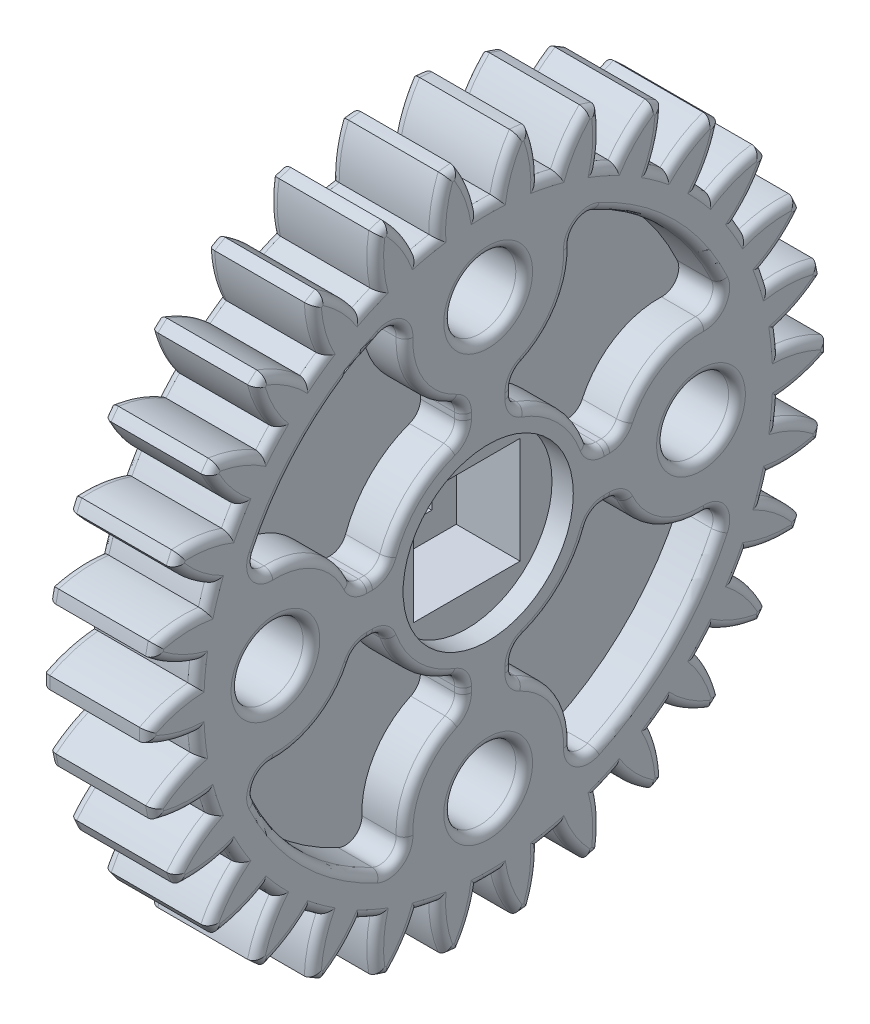
SolidWorks part; units mm, degrees
note: The reader was unsure of these and kept them because the rebuilt part matched: shared geometry of "Sketch2<4>", "Sketch3<3>".
ref_plane "Plane1" through (0, 0, 0) normal (0, 0, 1) x (1, 0, 0)
ref_plane "Plane2" through (0, 0, 0) normal (0, 1, 0) x (1, 0, 0)
ref_plane "Plane3" through (0, 0, 0) normal (1, 0, 0) x (0, 0, -1)
sketch "HoldingSke" plane through (0, 0, 0) normal (0, 1, 0) x (1, 0, 0)
  line L0 (0, 0) -> (439.9409, -254)
  line L1 (-15, 0) -> (100, 0) construction
  line L2 (0, 0) -> (-2.1039, 2.3779)
  line L3 (0, 0) -> (-11.863, 4.5341)
  line L4 (0, 0) -> (7.479, 4.318)
  line L5 (0, 0) -> (-47.5972, -17.7524)
  line L6 (0, 0) -> (-5.2639, -3.5516)
  line L7 (-2.1039, 2.3779) -> (8.8308, 51.9871)
  line L8 (-76.2, 54.61) -> (-74.422, 54.61)
  line L9 (-71.009, 38.7566) -> (-53.1078, 45.2721)
  line L10 (-76.2, 71.12) -> (104.1128, 71.12)
  line L11 (0, 0) -> (-6.35, 0)
  line L12 (-76.2, 101.6) -> (-76.1492, 101.6)
  line L13 (24.9733, 27.94) -> (52.9518, 28.4284)
  line L14 (24.9733, 27.94) -> (25.0241, 27.9398)
  line L15 (24.9733, 27.94) -> (100.4021, 29.52)
  circle A0 centre (0, 0) radius 0.7937
  circle A1 centre (0, 0) radius 17.4752
  circle A2 centre (0, 0) radius 38.1
  circle A3 centre (0, 0) radius 0.7937
  dimension "MHD" = 34.9504
  dimension "Hub_dia" = 76.2
  dimension "Bore" = 1.5875
  dimension "MBD" = 1.5875
  dimension "Num_teeth" = 30
  dimension "Pitch" = 508
  dimension "Overall_len" = 50.8
  dimension "Show_teeth" = 30
  dimension "Thickness" = 6.35
  dimension "OAL" = 50.8001
  dimension "T_dim" = 1.778
  dimension "Ap" = 20
  dimension "H" = 19.05
  dimension "Pitch_radius" = 180.3128
  dimension "Width" = 6.35
  dimension "Backlash" = 0.0508
  dimension "Addendum_fac" = 1
  dimension "Dedendum_fac" = 1.2
  dimension "Clearance_fac" = 0.2
  dimension "Dedendum_add" = 0.0508
sketch "BasProSke" plane through (0, 0, 0) normal (0, 1, 0) x (1, 0, 0)
  line L0 (-10, 0) -> (60, 0) construction
  line L1 (0, 0) -> (0, 20.32)
  line L2 (0, 0) -> (6.35, 0)
  line L3 (6.35, 0) -> (6.35, 20.32)
  line L4 (6.35, 20.32) -> (0, 20.32)
  dimension "Thickness" = 6.35
  dimension "Diameter" = 40.64
revolve "Base-Revolve" add sketch "BasProSke" angle 360 about L0
sketch "TooCutSke" plane through (0, 0, 0) normal (1, 0, 0) x (0, 0, -1)
  line L1 (0, 0) -> (0, 107) construction
  line L2 (0, 0) -> (-1.0859, 19.019) construction
  line L3 (0, 0) -> (-3.978, 37.8482) construction
  line L4 (-1.0859, 19.019) -> (-1.989, 18.9241) construction
  arc A0 (0.5992, 17.4649) -> (-0.5992, 17.4649) centre (0, 0) ccw
  arc A1 (1.7751, 20.2678) -> (-1.7751, 20.2678) centre (0, 0) ccw
  circle A2 centre (0, 0) radius 19.05 construction
  circle A3 centre (0, 0) radius 17.9011 construction
  arc A4 (-0.5992, 17.4649) -> (-1.7751, 20.2678) centre (-8.0726, 15.9776) ccw
  arc A5 (1.7751, 20.2678) -> (0.5992, 17.4649) centre (8.0726, 15.9776) ccw
  dimension "Root_dia" = 34.9504
  dimension "Overcut_dia" = 40.6908
  dimension "Pitch_dia" = 38.1
  dimension "Base_dia" = 35.8023
  dimension "Flank_rad" = 7.62
  dimension "Half_ang" = 6
  dimension "Half_CT" = 0.9081
extrude "ToothCut" cut sketch "TooCutSke" along normal through all
fillet "Breaks" [suppressed] radius 0.0254
fillet "RootFillets" [suppressed] radius 0.3048
pattern_circular "TeethCuts" count 30 every 12 about axis through (-10, 0, 0) along (1, 0, 0) of "ToothCut", "RootFillets", "Breaks"
sketch "HubNeaOneSke" plane through (0, 0, 0) normal (-1, 0, 0) x (0, 0, 1)
  circle A0 centre (0, 0) radius 17.4752
  dimension "Diameter" = 34.9504
extrude "HubNearOne" [suppressed] add sketch "HubNeaOneSke" along normal blind 44.4501
sketch "HubNeaBotSke" plane through (0, 0, 0) normal (-1, 0, 0) x (0, 0, 1)
  circle A0 centre (0, 0) radius 17.4752
  dimension "Diameter" = 34.9504
extrude "HubNearBoth" [suppressed] add sketch "HubNeaBotSke" along normal blind 22.225
ref_plane "FarPln" through (6.35, 0, 0) normal (1, 0, 0) x (0, 0, -1)
sketch "HubFarSke" plane through (6.35, 0, 0) normal (1, 0, 0) x (0, 0, -1)
  circle A0 centre (0, 0) radius 17.4752
  dimension "Diameter" = 34.9504
extrude "HubFar" [suppressed] add sketch "HubFarSke" along normal blind 22.225
sketch "BorSke" plane through (0, 0, 0) normal (1, 0, 0) x (0, 0, -1)
  circle A0 centre (0, 0) radius 0.7937
  dimension "Diameter" = 1.5875
extrude "Bore" cut sketch "BorSke" along normal mid plane 101.6001
sketch "KeySke" plane through (0, 0, 0) normal (1, 0, 0) x (0, 0, -1)
  line L0 (-0.127, 0) -> (-0.127, 0.9843)
  line L1 (-0.127, 0.9843) -> (0.127, 0.9843)
  line L2 (0.127, 0.9843) -> (0.127, 0)
  line L3 (0, 0) -> (0, 34) construction
  line L4 (-0.127, 0) -> (0.127, 0)
  dimension "Offset" = 0.9843
  dimension "Width" = 0.254
extrude "Keyway" [suppressed] cut sketch "KeySke" along normal mid plane 101.6001
pattern_circular "Keyway2" [suppressed] count 2 every 90 about axis through (-10, 0, 0) along (1, 0, 0)
sketch "Sketch1" plane through (6.35, 0, 0) normal (1, 0, 0) x (0, 0, -1)
  line L1 (1.7145, 1.7145) -> (-1.7145, 1.7145)
  line L2 (1.7145, 1.7145) -> (1.7145, -1.7145)
  line L3 (1.7145, -1.7145) -> (-1.7145, -1.7145)
  line L4 (-1.7145, 1.7145) -> (-1.7145, -1.7145)
  line L5 (1.7145, 1.7145) -> (-1.7145, -1.7145) construction
  line L6 (1.7145, -1.7145) -> (-1.7145, 1.7145) construction
  point P0 (0, 0)
  dimension "D1" = 3.429
extrude "Cut-Extrude1" cut sketch "Sketch1" against normal up to next
sketch "Sketch2" plane through (6.35, 0, 0) normal (1, 0, 0) x (0, 0, -1)
  line L0 (0, 0) -> (0, 10.2796) construction
  line L1 (-7.9303, -1.5) -> (-6.1703, -1.5)
  line L2 (-7.9303, 1.5) -> (-6.1703, 1.5)
  line L3 (1.5, -7.9303) -> (1.5, -6.1703)
  line L4 (-1.5, 7.9303) -> (-1.5, 6.1703)
  line L5 (1.5, 7.9303) -> (1.5, 6.1703)
  line L6 (7.9303, 1.5) -> (6.1703, 1.5)
  line L7 (7.9303, -1.5) -> (6.1703, -1.5)
  line L17 (-1.5, -7.9303) -> (-1.5, -6.1703)
  circle A0 centre (0, 0) radius 6.35
  circle A1 centre (0, 0) radius 15.24
  arc A2 (4.661, -14.5097) -> (1.5, -7.9303) centre (0, -12.7) ccw
  circle A3 centre (0, -12.7) radius 2.15
  arc A4 (-1.5, -7.9303) -> (-4.661, -14.5097) centre (0, -12.7) ccw
  arc A5 (-14.5097, -4.661) -> (-7.9303, -1.5) centre (-12.7, 0) ccw
  circle A6 centre (-12.7, 0) radius 2.15
  arc A7 (-7.9303, 1.5) -> (-14.5097, 4.661) centre (-12.7, 0) ccw
  arc A8 (-4.661, 14.5097) -> (-1.5, 7.9303) centre (0, 12.7) ccw
  circle A9 centre (0, 12.7) radius 2.15
  arc A10 (1.5, 7.9303) -> (4.661, 14.5097) centre (0, 12.7) ccw
  arc A11 (14.5097, 4.661) -> (7.9303, 1.5) centre (12.7, 0) ccw
  circle A12 centre (12.7, 0) radius 2.15
  arc A13 (7.9303, -1.5) -> (14.5097, -4.661) centre (12.7, 0) ccw
  dimension "D2" = 12.7
  dimension "D3" = 30.48
  dimension "D1" = 4.3
  dimension "D6" = 5
  dimension "D5" = 12.7
  dimension "D4" = 3
  dimension "D7" = 4
extrude "Cut-Extrude2" cut sketch "Sketch2" against normal through all contours A5 A1 A4 L17 A0 L1 | A13 L7 A0 L3 A2 A1 | A11 A1 A10 L5 A0 L6 | A8 A1 A7 L2 A0 L4 | A6 | L0 A3 | A3 L0 | A12 | L0 A9 | A9 L0
fillet "Fillet2" radius 1 24 edges at (3.175, -6.1703, -1.5) (3.175, -4.661, -14.5097) (3.175, -14.5097, -4.661) (3.175, -7.9303, -1.5) (3.175, -1.5, -6.1703) (3.175, -1.5, -7.9303) (3.175, 4.661, -14.5097) (3.175, 1.5, -7.9303) (3.175, 1.5, -6.1703) (3.175, 6.1703, -1.5) (3.175, 7.9303, -1.5) (3.175, 14.5097, -4.661) (3.175, 14.5097, 4.661) (3.175, 7.9303, 1.5) (3.175, 6.1703, 1.5) (3.175, 4.661, 14.5097) (3.175, 1.5, 7.9303) (3.175, 1.5, 6.1703) (3.175, -14.5097, 4.661) (3.175, -7.9303, 1.5) (3.175, -4.661, 14.5097) (3.175, -1.5, 7.9303) (3.175, -6.1703, 1.5) (3.175, -1.5, 6.1703)
extrude "Boss-Extrude1" add sketch "Sketch2<4>" along normal mid plane 1.27 from offset 3.175 offset against normal yes
sketch "Sketch2<4>" plane through (6.35, 0, 0) normal (1, 0, 0) x (0, 0, -1) same geometry as "Sketch2"
fillet "Fillet3" radius 0.5 352 edges at (0, -3.0115, 18.6998) (6.35, 19.3255, -6.2792) (6.35, 17.5976, -10.16) (6.35, 15.1007, -13.5967) (6.35, 11.9438, -16.4392) (6.35, 8.2649, -18.5632) (6.35, 4.2248, -19.876) (6.35, 0, -20.32) (6.35, -4.2248, -19.876) (6.35, -8.2649, -18.5632) (6.35, -11.9438, -16.4392) (6.35, -15.1007, -13.5967) (6.35, -17.5976, -10.16) (6.35, 20.2087, -2.124) (6.35, -19.3255, -6.2792) (6.35, -20.2087, -2.124) (6.35, -20.2087, 2.124) (6.35, -19.3255, 6.2792) (6.35, -17.5976, 10.16) (6.35, -15.1007, 13.5967) (6.35, -11.9438, 16.4392) (6.35, -8.2649, 18.5632) (6.35, -4.2248, 19.876) (6.35, 0, 20.32) (6.35, 4.2248, 19.876) (6.35, 8.2649, 18.5632) (6.35, 11.9438, 16.4392) (6.35, 15.1007, 13.5967) (6.35, 17.5976, 10.16) (6.35, 19.3255, 6.2792) (6.35, 18.9122, -1.0403) (6.35, 18.9122, 1.0403) (6.35, 17.4752, 0) (0, 18.9122, -1.0403) (0, 17.4752, 0) (6.35, -0.9422, 18.9173) (6.35, -3.0115, 18.6998) (6.35, -1.8267, 17.3795) (0, -0.9422, 18.9173) (0, -1.8267, 17.3795) (6.35, 3.0115, 18.6998) (6.35, 0.9422, 18.9173) (6.35, 1.8267, 17.3795) (0, 3.0115, 18.6998) (0, 1.8267, 17.3795) (6.35, 6.8336, 17.6651) (6.35, 4.8548, 18.308) (6.35, 5.4001, 16.6199) (0, 6.8336, 17.6651) (0, 5.4001, 16.6199) (6.35, 10.357, 15.8583) (6.35, 8.5551, 16.8986) (6.35, 8.7376, 15.134) (0, 10.357, 15.8583) (0, 8.7376, 15.134) (6.35, 17.7003, 6.7419) (6.35, 16.854, 8.6427) (6.35, 15.9644, 7.1078) (0, 17.7003, 6.7419) (0, 15.9644, 7.1078) (6.35, 13.4278, 13.3584) (6.35, 11.8816, 14.7506) (6.35, 11.6932, 12.9866) (0, 13.4278, 13.3584) (0, 11.6932, 12.9866) (6.35, 15.9118, 10.2747) (6.35, 14.6888, 11.9579) (6.35, 14.1377, 10.2717) (0, 15.9118, 10.2747) (0, 14.1377, 10.2717) (6.35, -18.9122, 1.0403) (6.35, -18.9122, -1.0403) (6.35, -17.4752, 0) (0, -18.9122, 1.0403) (0, -17.4752, 0) (6.35, -18.2826, 4.9497) (6.35, -18.7152, 2.9145) (6.35, -17.0933, 3.6333) (0, -18.2826, 4.9497) (0, -17.0933, 3.6333) (6.35, -14.6888, 11.9579) (6.35, -15.9118, 10.2747) (6.35, -14.1377, 10.2717) (0, -14.6888, 11.9579) (0, -14.1377, 10.2717) (6.35, -16.854, 8.6427) (6.35, -17.7003, 6.7419) (6.35, -15.9644, 7.1078) (0, -16.854, 8.6427) (0, -15.9644, 7.1078) (0, 20.2087, 2.124) (6.35, -8.5551, 16.8986) (6.35, -10.357, 15.8583) (6.35, -8.7376, 15.134) (0, -8.5551, 16.8986) (0, -8.7376, 15.134) (0, 18.2826, 4.9497) (6.35, -11.8816, 14.7506) (6.35, -13.4278, 13.3584) (6.35, -11.6932, 12.9866) (0, -11.8816, 14.7506) (0, -11.6932, 12.9866) (6.35, 20.2087, 2.124) (6.35, -4.8548, 18.308) (6.35, -6.8336, 17.6651) (6.35, -5.4001, 16.6199) (0, -4.8548, 18.308) (0, -5.4001, 16.6199) (6.35, -3.0115, -18.6998) (6.35, -0.9422, -18.9173) (6.35, -1.8267, -17.3795) (0, -3.0115, -18.6998) (0, -1.8267, -17.3795) (6.35, -6.8336, -17.6651) (6.35, -4.8548, -18.308) (6.35, -5.4001, -16.6199) (0, -6.8336, -17.6651) (0, -5.4001, -16.6199) (6.35, 18.7152, 2.9145) (6.35, 18.2826, 4.9497) (6.35, -13.4278, -13.3584) (6.35, -11.8816, -14.7506) (6.35, -11.6932, -12.9866) (6.35, 17.0933, 3.6333) (0, -13.4278, -13.3584) (0, -11.6932, -12.9866) (0, 18.7152, 2.9145) (6.35, -10.357, -15.8583) (6.35, -8.5551, -16.8986) (6.35, -8.7376, -15.134) (0, -10.357, -15.8583) (0, -8.7376, -15.134) (6.35, -17.7003, -6.7419) (6.35, -16.854, -8.6427) (6.35, -15.9644, -7.1078) (0, -17.7003, -6.7419) (0, -15.9644, -7.1078) (0, 17.0933, 3.6333) (6.35, -15.9118, -10.2747) (6.35, -14.6888, -11.9579) (6.35, -14.1377, -10.2717) (0, -15.9118, -10.2747) (0, -14.1377, -10.2717) (6.35, -18.7152, -2.9145) (6.35, -18.2826, -4.9497) (6.35, -17.0933, -3.6333) (0, -18.7152, -2.9145) (0, -17.0933, -3.6333) (6.35, 14.6888, -11.9579) (6.35, 15.9118, -10.2747) (6.35, 14.1377, -10.2717) (0, 14.6888, -11.9579) (0, 14.1377, -10.2717) (6.35, 11.8816, -14.7506) (6.35, 13.4278, -13.3584) (6.35, 11.6932, -12.9866) (0, 11.8816, -14.7506) (0, 11.6932, -12.9866) (6.35, 16.854, -8.6427) (6.35, 17.7003, -6.7419) (6.35, 15.9644, -7.1078) (0, 16.854, -8.6427) (0, 15.9644, -7.1078) (6.35, 18.2826, -4.9497) (6.35, 18.7152, -2.9145) (6.35, 17.0933, -3.6333) (0, 18.2826, -4.9497) (0, 17.0933, -3.6333) (6.35, 8.5551, -16.8986) (6.35, 10.357, -15.8583) (6.35, 8.7376, -15.134) (0, 8.5551, -16.8986) (0, 8.7376, -15.134) (6.35, 4.8548, -18.308) (6.35, 6.8336, -17.6651) (6.35, 5.4001, -16.6199) (0, 4.8548, -18.308) (0, 5.4001, -16.6199) (6.35, 0.9422, -18.9173) (6.35, 3.0115, -18.6998) (6.35, 1.8267, -17.3795) (0, 0.9422, -18.9173) (0, 1.8267, -17.3795) (0, 19.3255, -6.2792) (0, 17.5976, -10.16) (0, 15.1007, -13.5967) (0, 11.9438, -16.4392) (0, 8.2649, -18.5632) (0, 4.2248, -19.876) (0, 0, -20.32) (0, -4.2248, -19.876) (0, -8.2649, -18.5632) (0, -11.9438, -16.4392) (0, -15.1007, -13.5967) (0, -17.5976, -10.16) (0, -19.3255, -6.2792) (0, -20.2087, -2.124) (0, -20.2087, 2.124) (0, -19.3255, 6.2792) (0, -17.5976, 10.16) (0, -15.1007, 13.5967) (0, -11.9438, 16.4392) (0, -8.2649, 18.5632) (0, -4.2248, 19.876) (0, 0, 20.32) (0, -1.7145, 0) (0, 0, 1.7145) (0, 1.7145, 0) (0, 0, -1.7145) (6.35, 0, 1.7145) (6.35, -1.7145, 0) (6.35, 0, -1.7145) (6.35, 1.7145, 0) (0, 4.2248, 19.876) (0, 8.2649, 18.5632) (0, 11.9438, 16.4392) (0, 15.1007, 13.5967) (0, 17.5976, 10.16) (0, 19.3255, 6.2792) (0, 3.0115, -18.6998) (0, 0, 10.55) (6.35, 0, 10.55) (0, 6.8336, -17.6651) (0, -12.7, -2.15) (6.35, -12.7, -2.15) (0, 0, -14.85) (6.35, 0, -14.85) (0, 12.7, -2.15) (0, 10.357, -15.8583) (6.35, 12.7, -2.15) (0, 18.7152, -2.9145) (0, 17.7003, -6.7419) (0, 13.4278, -13.3584) (6.35, -4.2561, -10.0759) (0, -4.2561, -10.0759) (6.35, -10.7763, -10.7763) (0, -10.7763, -10.7763) (6.35, -10.0759, -4.2561) (0, -10.0759, -4.2561) (6.35, -7.0787, -1.5) (0, -7.0787, -1.5) (6.35, -4.4901, -4.4901) (0, -4.4901, -4.4901) (6.35, -1.5, -7.0787) (0, -1.5, -7.0787) (6.35, 10.7763, -10.7763) (0, 15.9118, -10.2747) (0, 10.7763, -10.7763) (6.35, 4.2561, -10.0759) (0, 4.2561, -10.0759) (6.35, 1.5, -7.0787) (0, 1.5, -7.0787) (6.35, 4.4901, -4.4901) (0, 4.4901, -4.4901) (6.35, 7.0787, -1.5) (0, 7.0787, -1.5) (6.35, 10.0759, -4.2561) (0, 10.0759, -4.2561) (6.35, 10.7763, 10.7763) (0, 10.7763, 10.7763) (0, -18.2826, -4.9497) (6.35, 10.0759, 4.2561) (0, 10.0759, 4.2561) (6.35, 7.0787, 1.5) (0, 7.0787, 1.5) (6.35, 4.4901, 4.4901) (0, 4.4901, 4.4901) (6.35, 4.2561, 10.0759) (0, 4.2561, 10.0759) (6.35, 1.5, 7.0787) (0, 1.5, 7.0787) (6.35, -10.0759, 4.2561) (0, -10.0759, 4.2561) (0, -14.6888, -11.9579) (6.35, -10.7763, 10.7763) (0, -10.7763, 10.7763) (6.35, -7.0787, 1.5) (0, -7.0787, 1.5) (6.35, -4.2561, 10.0759) (0, -4.2561, 10.0759) (6.35, -1.5, 7.0787) (0, -1.5, 7.0787) (6.35, -4.4901, 4.4901) (0, -4.4901, 4.4901) (6.35, -5.443, -13.7492) (0, -5.443, -13.7492) (6.35, -13.7492, -5.443) (0, -13.7492, -5.443) (6.35, -7.7857, -1.6584) (0, -7.7857, -1.6584) (6.35, -6.3374, -1.6814) (0, -16.854, -8.6427) (0, -6.3374, -1.6814) (6.35, -1.6814, -6.3374) (0, -1.6814, -6.3374) (6.35, -1.6584, -7.7857) (0, -1.6584, -7.7857) (6.35, 5.443, -13.7492) (0, 5.443, -13.7492) (6.35, 1.6584, -7.7857) (0, 1.6584, -7.7857) (6.35, 1.6814, -6.3374) (0, 1.6814, -6.3374) (6.35, 6.3374, -1.6814) (0, 6.3374, -1.6814) (6.35, 7.7857, -1.6584) (0, 7.7857, -1.6584) (6.35, 13.7492, -5.443) (0, 13.7492, -5.443) (6.35, 13.7492, 5.443) (0, 13.7492, 5.443) (6.35, 7.7857, 1.6584) (0, 7.7857, 1.6584) (6.35, 6.3374, 1.6814) (0, 6.3374, 1.6814) (6.35, 5.443, 13.7492) (0, 5.443, 13.7492) (6.35, 1.6584, 7.7857) (0, 1.6584, 7.7857) (6.35, 1.6814, 6.3374) (0, 1.6814, 6.3374) (6.35, -13.7492, 5.443) (0, -13.7492, 5.443) (6.35, -7.7857, 1.6584) (0, -7.7857, 1.6584) (6.35, -5.443, 13.7492) (0, -5.443, 13.7492) (0, -8.5551, -16.8986) (6.35, -1.6584, 7.7857) (0, -1.6584, 7.7857) (6.35, -6.3374, 1.6814) (0, -6.3374, 1.6814) (6.35, -1.6814, 6.3374) (0, -1.6814, 6.3374) (0, -11.8816, -14.7506) (0, -4.8548, -18.308) (0, -0.9422, -18.9173) (0, -6.8336, 17.6651) (0, -13.4278, 13.3584) (0, -10.357, 15.8583) (0, -17.7003, 6.7419) (0, -15.9118, 10.2747) (0, -18.7152, 2.9145) (0, 20.2087, -2.124) (0, -18.9122, -1.0403) (0, 14.6888, 11.9579) (0, 11.8816, 14.7506) (0, 16.854, 8.6427) (0, 8.5551, 16.8986) (0, 4.8548, 18.308) (0, 18.9122, 1.0403) (0, 0.9422, 18.9173)
sketch "Sketch3" plane through (6.35, 0, 0) normal (1, 0, 0) x (0, 0, -1)
  line L1 (-3.175, -3.175) -> (3.175, -3.175)
  line L2 (-3.175, -3.175) -> (-3.175, 3.175)
  line L3 (-3.175, 3.175) -> (3.175, 3.175)
  line L4 (3.175, -3.175) -> (3.175, 3.175)
  line L5 (-3.175, -3.175) -> (3.175, 3.175) construction
  line L6 (-3.175, 3.175) -> (3.175, -3.175) construction
  circle A0 centre (0, 0) radius 5.08
  dimension "D2" = 10.16
  dimension "D1" = 6.35
extrude "Cut-Extrude3" cut sketch "Sketch3" against normal blind 1.27 contours A0 L4 L1 L2 L3 | L1 L4 L3 L2
extrude "Cut-Extrude4" cut sketch "Sketch3<3>" against normal blind 5.08 contours L1 L4 L3 L2
sketch "Sketch3<3>" plane through (6.35, 0, 0) normal (1, 0, 0) x (0, 0, -1) same geometry as "Sketch3"
equation "' \"Pitch@HoldingSke\" = 4"
equation "' \"Num_teeth@HoldingSke\" = 12"
equation "' \"Ap@HoldingSke\" =  20"
equation "' \"Ap@HoldingSke\" = 20"
equation "' \"Width@HoldingSke\" = 0.5"
equation "' \"Hub_dia@HoldingSke\"= 1"
equation "' \"Hub_dia@HoldingSke\" = 1"
equation "' \"Overall_len@HoldingSke\" = 1.0"
equation "' \"Bore@HoldingSke\" = 0.75"
equation "' \"T_dim@HoldingSke\" = 0.85"
equation "' \"Width@KeySke\" = 0.25"
equation "' \"Show_teeth@HoldingSke\" = 13"
equation "' \"Backlash@HoldingSke\" = 0.009"
equation "' \"Addendum_fac@HoldingSke\" = 1.0"
equation "' \"Dedendum_fac@HoldingSke\" = 1.25"
equation "' \"Dedendum_add@HoldingSke\" = 0.00005"
equation "' \"Clearance_fac@HoldingSke\" = 0.25"
equation "' \"Pitch@HoldingSke\" = 0.5"
equation "' \"Num_teeth@HoldingSke\" = 23"
equation "' \"Show_teeth@HoldingSke\" = 23"
equation "' \"Backlash@HoldingSke\" = 0.0375"
equation "\"Overcut_dia@TooCutSke\" = (\"Num_teeth@HoldingSke\" + 2 * \"Addendum_fac@HoldingSke\") / \"Pitch@HoldingSke\" + 0.002"
equation "\"Pitch_dia@TooCutSke\" = \"Num_teeth@HoldingSke\" / \"Pitch@HoldingSke\""
equation "\"Base_dia@TooCutSke\" = \"Num_teeth@HoldingSke\" / \"Pitch@HoldingSke\" * cos((\"Ap@HoldingSke\"  * 3.14159265 / 180))"
equation "\"Root_dia@TooCutSke\" = (\"Num_teeth@HoldingSke\" + 2) / \"Pitch@HoldingSke\" - 2 * (\"Addendum_fac@HoldingSke\" + \"Dedendum_fac@HoldingSke\") / \"Pitch@HoldingSke\" - \"Dedendum_add@HoldingSke\" * 2"
equation "\"Half_ang@TooCutSke\" = 180 / \"Num_teeth@HoldingSke\""
equation "\"Half_CT@TooCutSke\" = \"Num_teeth@HoldingSke\" / \"Pitch@HoldingSke\" * sin((3.14159265 / 2 / \"Num_teeth@HoldingSke\")) / 2 - 7 * \"Backlash@HoldingSke\" / 4"
equation "\"Flank_rad@TooCutSke\" = \"Num_teeth@HoldingSke\" / \"Pitch@HoldingSke\" / 5"
equation "\"Radius@RootFillets\" = \"Clearance_fac@HoldingSke\" / \"Pitch@HoldingSke\" + \"Dedendum_add@HoldingSke\""
equation "\"Break_rad@Breaks\" = 0.02 / \"Pitch@HoldingSke\""
equation "\"Thickness@HoldingSke\" = \"Width@HoldingSke\""
equation "\"OAL@HoldingSke\" = \"Thickness@HoldingSke\""
equation "\"MHD@HoldingSke\" = (\"Num_teeth@HoldingSke\" + 2) / \"Pitch@HoldingSke\" - 2 * (\"Addendum_fac@HoldingSke\" + \"Dedendum_fac@HoldingSke\")  / \"Pitch@HoldingSke\" - \"Dedendum_add@HoldingSke\" * 2"
equation "\"MBD@HoldingSke\" = (\"Num_teeth@HoldingSke\" + 2) / \"Pitch@HoldingSke\" - 2 * (\"Addendum_fac@HoldingSke\" + \"Dedendum_fac@HoldingSke\")  / \"Pitch@HoldingSke\" - \"Dedendum_add@HoldingSke\" * 2 - 0.002"
equation "\"MHD@HoldingSke\" = ((sgn( \"MHD@HoldingSke\" - \"Hub_dia@HoldingSke\" )-1)*( \"MHD@HoldingSke\" - \"Hub_dia@HoldingSke\" ))/-2+ \"Hub_dia@HoldingSke\""
equation "\"MBD@HoldingSke\" = ((sgn( \"MBD@HoldingSke\" - \"Bore@HoldingSke\" )-1)*( \"MBD@HoldingSke\" - \"Bore@HoldingSke\" ))/-2+ \"Bore@HoldingSke\""
equation "\"OAL@HoldingSke\" = ((sgn( \"OAL@HoldingSke\" - \"Overall_len@HoldingSke\" )+1)*( \"OAL@HoldingSke\" - \"Overall_len@HoldingSke\" ))/2 + \"Overall_len@HoldingSke\" + 0.000002"
equation "\"Num_teeth@TeethCuts\" = int( \"Show_teeth@HoldingSke\" ) + 1"
equation "\"Num_teeth@TeethCuts\" = ((sgn( \"Num_teeth@TeethCuts\" - \"Num_teeth@HoldingSke\" )-1)*( \"Num_teeth@TeethCuts\" - \"Num_teeth@HoldingSke\" ))/-2+ \"Num_teeth@HoldingSke\""
equation "\"Num_teeth@TeethCuts\" = ((sgn( \"Num_teeth@TeethCuts\" - 2.0)+1)*( \"Num_teeth@TeethCuts\" - 2.0))/2 +2.0"
equation "\"Angle@TeethCuts\" = 360.0 / \"Num_teeth@HoldingSke\""
equation "\"Diameter@BasProSke\" = (\"Num_teeth@HoldingSke\" + 2 * \"Addendum_fac@HoldingSke\") / \"Pitch@HoldingSke\""
equation "\"Thickness@BasProSke\"  = \"Thickness@HoldingSke\""
equation "' \"Fillet_rad@BasProSke\" =  \"Thickness@HoldingSke\" * 0.05"
equation "' \"Fillet_rad@BasProSke\" = \"Thickness@HoldingSke\" * 0.05"
equation "\"MHD@HoldingSke\" = ((sgn( \"MHD@HoldingSke\" - \"Root_dia@TooCutSke\" )-1)*( \"MHD@HoldingSke\" - \"Root_dia@TooCutSke\" ))/-2+ \"Root_dia@TooCutSke\""
equation "\"Diameter@HubNeaOneSke\" = \"MHD@HoldingSke\""
equation "\"Length@HubNearOne\" = \"OAL@HoldingSke\" - \"Thickness@BasProSke\""
equation "\"Diameter@HubNeaBotSke\" = \"MHD@HoldingSke\""
equation "\"Length@HubNearBoth\" = ( \"OAL@HoldingSke\" - \"Thickness@BasProSke\" ) / 2.0"
equation "\"Thickness@FarPln\" = \"Thickness@BasProSke\""
equation "\"Diameter@HubFarSke\" = \"MHD@HoldingSke\""
equation "\"Length@HubFar\" = ( \"OAL@HoldingSke\" - \"Thickness@BasProSke\" ) / 2.0"
equation "\"Diameter@BorSke\" = \"MBD@HoldingSke\""
equation "\"D1@Bore\" = \"OAL@HoldingSke\" * 2.0"
equation "\"D1@Keyway\" = \"OAL@HoldingSke\" * 2.0"
equation "\"Offset@KeySke\" = \"T_dim@HoldingSke\" - \"MBD@HoldingSke\" / 2.0"
